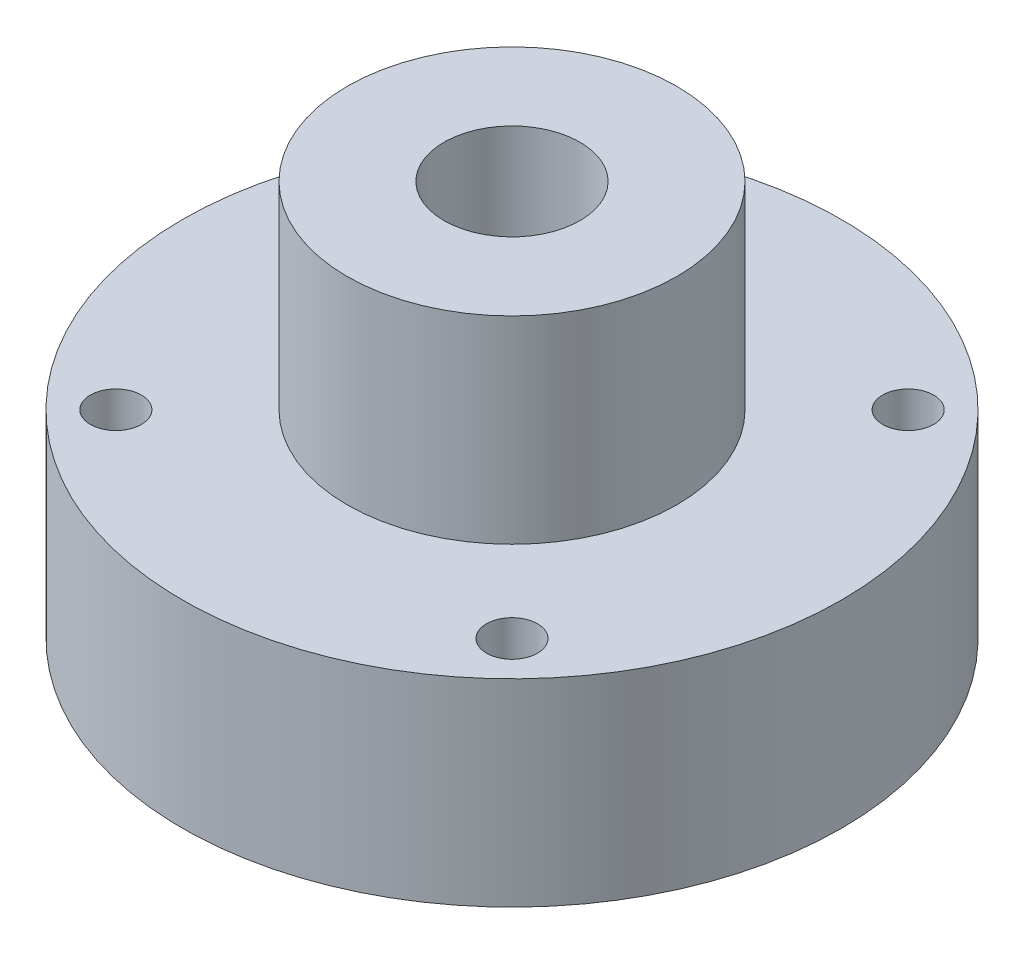
SolidWorks part; units mm, degrees
material "6061-T6 (SS)"
ref_plane "Front Plane" through (0, 0, 0) normal (0, 0, 1) x (1, 0, 0)
ref_plane "Top Plane" through (0, 0, 0) normal (0, 1, 0) x (1, 0, 0)
ref_plane "Right Plane" through (0, 0, 0) normal (1, 0, 0) x (0, 0, -1)
sketch "Sketch1" plane through (0, 0, 0) normal (0, 0, 1) x (1, 0, 0)
  line L0 (0, 0) -> (0, -5.2937) construction
  line L6 (-12.7, -19.05) -> (-12.7, -38.1)
  line L9 (-31.75, 0) -> (-31.75, -38.1)
  line L12 (-12.7, -19.05) -> (-3.175, -19.05)
  line L15 (-19.0373, -38.1) -> (-12.7, -38.1)
  line L17 (-31.75, -38.1) -> (-23.8125, -38.1)
  line L18 (-23.8125, -38.1) -> (-23.8125, -34.9631)
  line L19 (-23.8125, -34.9631) -> (-19.0373, -34.9631)
  line L20 (-19.0373, -34.9631) -> (-19.0373, -38.1)
  line L24 (-12.7, -38.1) -> (-3.175, -19.05)
  line L25 (-31.75, 0) -> (-3.175, 0)
  line L26 (-3.175, 0) -> (-3.175, -19.05)
  line L27 (-31.75, -19.05) -> (-15.875, -19.05)
  line L28 (-15.875, -19.05) -> (-15.875, 0)
  spline S0 degree 3 poles (6.8653, -14.0383) (6.7746, -14.0297) (6.669, -14.0211) (6.2404, -13.9904) (5.8365, -13.9684) (4.8724, -13.9243) (4.3124, -13.9022) (3.084, -13.8581) (2.4159, -13.8361) (1.0289, -13.792) (0.3103, -13.77) (-1.1159, -13.7259) (-1.8233, -13.7038) (-3.1659, -13.6597) (-3.8009, -13.6377) (-4.9442, -13.5936) (-5.4523, -13.5715) (-6.2976, -13.5274) (-6.6348, -13.5054) (-7.1093, -13.4613) (-7.3837, -13.4172) (-7.2343, -13.3731) (-6.8792, -13.329) (-6.5989, -13.3069) (-5.8566, -13.2628) (-5.3947, -13.2408) (-4.3289, -13.1967) (-3.7251, -13.1746) (-2.4274, -13.1305) (-1.7337, -13.1085) (-0.3158, -13.0644) (0.4082, -13.0423) (1.8242, -12.9983) (2.5161, -12.9762) (3.8083, -12.9321) (4.4084, -12.9101) (5.4653, -12.866) (5.922, -12.8439) (6.6525, -12.7998) (6.9263, -12.7778) (7.2673, -12.7337) (7.4017, -12.6896) (7.1111, -12.6455) (6.6204, -12.6014) (6.275, -12.5793) (5.4137, -12.5352) (4.8979, -12.5132) (3.74, -12.4691) (3.0981, -12.447) (1.7433, -12.4029) (1.0305, -12.3809) (-0.4048, -12.3368) (-1.1271, -12.3147) (-2.5192, -12.2706) (-3.1888, -12.2486) (-4.4177, -12.2045) (-4.9769, -12.1825) (-5.9368, -12.1384) (-6.3373, -12.1163) (-6.9452, -12.0722) (-7.1525, -12.0502) (-7.3559, -12.0061) (-7.352, -11.984) (-7.1332, -11.9399) (-6.9183, -11.9179) (-6.2959, -11.8738) (-5.8884, -11.8517) (-4.9158, -11.8076) (-4.3507, -11.7856) (-3.1114, -11.7415) (-2.4374, -11.7194) (-1.0381, -11.6753) (-0.313, -11.6533) (1.1259, -11.6092) (1.8395, -11.5871) (3.194, -11.543) (3.8347, -11.521) (4.9881, -11.4769) (5.5007, -11.4548) (6.3536, -11.4108) (6.6938, -11.3887) (7.1724, -11.3446) (7.4493, -11.3005) (7.2985, -11.2564) (6.9403, -11.2123) (6.6574, -11.1903) (5.9085, -11.1462) (5.4425, -11.1241) (4.3673, -11.08) (3.7581, -11.058) (2.4489, -11.0139) (1.749, -10.9918) (0.3186, -10.9477) (-0.4118, -10.9257) (-1.8404, -10.8816) (-2.5384, -10.8595) (-3.842, -10.8154) (-4.4475, -10.7934) (-5.5138, -10.7493) (-5.9745, -10.7272) (-6.7114, -10.6831) (-6.9876, -10.6611) (-7.3316, -10.617) (-7.4672, -10.5729) (-7.174, -10.5288) (-6.679, -10.4847) (-6.3305, -10.4627) (-5.4616, -10.4186) (-4.9412, -10.3965) (-3.7731, -10.3524) (-3.1255, -10.3304) (-1.7587, -10.2863) (-1.0396, -10.2642) (0.4084, -10.2201) (1.1371, -10.1981) (2.5414, -10.154) (3.217, -10.1319) (4.4567, -10.0878) (5.0209, -10.0658) (5.9892, -10.0217) (6.3932, -9.9996) (7.0065, -9.9555) (7.2156, -9.9335) (7.4209, -9.8894) (7.4169, -9.8673) (7.1962, -9.8233) (6.9794, -9.8012) (6.3515, -9.7571) (5.9404, -9.7351) (4.9591, -9.691) (4.3891, -9.6689) (3.1389, -9.6248) (2.4589, -9.6028) (1.0472, -9.5587) (0.3158, -9.5366) (-1.1358, -9.4925) (-1.8557, -9.4705) (-3.2221, -9.4264) (-3.8685, -9.4043) (-5.0321, -9.3602) (-5.5491, -9.3382) (-6.4095, -9.2941) (-6.7527, -9.272) (-7.2356, -9.2279) (-7.5148, -9.1838) (-7.3627, -9.1397) (-7.0013, -9.0956) (-6.716, -9.0736) (-5.9605, -9.0295) (-5.4904, -9.0075) (-4.4056, -8.9634) (-3.7911, -8.9413) (-2.4704, -8.8972) (-1.7644, -8.8752) (-0.3214, -8.8311) (0.4154, -8.809) (1.8566, -8.7649) (2.5607, -8.7429) (3.8757, -8.6988) (4.4865, -8.6767) (5.5622, -8.6326) (6.0269, -8.6106) (6.7704, -8.5665) (7.049, -8.5444) (7.396, -8.5003) (7.5327, -8.4562) (7.237, -8.4121) (6.7375, -8.368) (6.386, -8.346) (5.5095, -8.3019) (4.9846, -8.2798) (3.8062, -8.2358) (3.1529, -8.2137) (1.7741, -8.1696) (1.0487, -8.1476) (-0.412, -8.1035) (-1.147, -8.0814) (-2.5637, -8.0373) (-3.2451, -8.0153) (-4.4958, -7.9712) (-5.0648, -7.9491) (-6.0416, -7.905) (-6.4492, -7.883) (-7.0678, -7.8389) (-7.2788, -7.8168) (-7.4858, -7.7727) (-7.4818, -7.7507) (-7.2591, -7.7066) (-7.0404, -7.6845) (-6.407, -7.6404) (-5.9923, -7.6184) (-5.0025, -7.5743) (-4.4275, -7.5522) (-3.1663, -7.5081) (-2.4803, -7.4861) (-1.0564, -7.442) (-0.3185, -7.42) (1.1457, -7.3759) (1.8719, -7.3538) (3.2503, -7.3097) (3.9023, -7.2877) (5.076, -7.2436) (5.5976, -7.2215) (6.4655, -7.1774) (6.8116, -7.1554) (7.2987, -7.1113) (7.5804, -7.0672) (7.4269, -7.0231) (7.0624, -6.979) (6.7746, -6.9569) (6.0125, -6.9128) (5.5382, -6.8908) (4.444, -6.8467) (3.8242, -6.8246) (2.492, -6.7805) (1.7798, -6.7585) (0.3242, -6.7144) (-0.4191, -6.6923) (-1.8727, -6.6483) (-2.583, -6.6262) (-3.9095, -6.5821) (-4.5256, -6.5601) (-5.6106, -6.516) (-6.0794, -6.4939) (-6.8293, -6.4498) (-7.1103, -6.4278) (-7.4603, -6.3837) (-7.5982, -6.3396) (-7.2999, -6.2955) (-6.7961, -6.2514) (-6.4416, -6.2293) (-5.5574, -6.1852) (-5.0279, -6.1632) (-3.8393, -6.1191) (-3.1803, -6.097) (-1.7895, -6.0529) (-1.0578, -6.0309) (0.4155, -5.9868) (1.157, -5.9647) (2.586, -5.9206) (3.2733, -5.8986) (4.5348, -5.8545) (5.1088, -5.8325) (6.094, -5.7884) (6.5052, -5.7663) (7.1291, -5.7222) (7.3419, -5.7002) (7.5507, -5.6561) (7.5467, -5.634) (7.322, -5.5899) (7.1015, -5.5679) (6.4625, -5.5238) (6.0443, -5.5017) (5.0458, -5.4576) (4.4658, -5.4356) (3.1937, -5.3915) (2.5018, -5.3694) (1.0655, -5.3253) (0.3213, -5.3033) (-1.1556, -5.2592) (-1.8881, -5.2371) (-3.2784, -5.193) (-3.936, -5.171) (-5.1199, -5.1269) (-5.646, -5.1048) (-6.5214, -5.0608) (-6.8705, -5.0387) (-7.3618, -4.9946) (-7.6459, -4.9505) (-7.4912, -4.9064) (-7.1234, -4.8623) (-6.8331, -4.8403) (-6.0644, -4.7962) (-5.5861, -4.7741) (-4.4824, -4.73) (-3.8572, -4.708) (-2.5135, -4.6639) (-1.7951, -4.6418) (-0.327, -4.5977) (0.4227, -4.5757) (1.8889, -4.5316) (2.6053, -4.5095) (3.9432, -4.4654) (4.5646, -4.4434) (5.659, -4.3993) (6.1318, -4.3772) (6.8882, -4.3331) (7.1716, -4.3111) (7.5246, -4.267) (7.6637, -4.2229) (7.3628, -4.1788) (6.8547, -4.1347) (6.4971, -4.1127) (5.6053, -4.0686) (5.0712, -4.0465) (3.8723, -4.0024) (3.2077, -3.9804) (1.8049, -3.9363) (1.0669, -3.9142) (-0.4191, -3.8701) (-1.167, -3.8481) (-2.6082, -3.804) (-3.3015, -3.7819) (-4.5226, -3.7396) (-5.0592, -3.7193) (-5.5281, -3.6991) knots 0.041447 0.041447 0.041447 0.041447 0.042969 0.042969 0.046875 0.046875 0.050781 0.050781 0.054688 0.054688 0.058594 0.058594 0.0625 0.0625 0.066406 0.066406 0.070312 0.070312 0.074219 0.074219 0.078125 0.082031 0.082031 0.085938 0.085938 0.089844 0.089844 0.09375 0.09375 0.097656 0.097656 0.101562 0.101562 0.105469 0.105469 0.109375 0.109375 0.113281 0.113281 0.117188 0.117188 0.121094 0.125 0.125 0.128906 0.128906 0.132812 0.132812 0.136719 0.136719 0.140625 0.140625 0.144531 0.144531 0.148438 0.148438 0.152344 0.152344 0.15625 0.15625 0.160156 0.160156 0.164062 0.164062 0.167969 0.167969 0.171875 0.171875 0.175781 0.175781 0.179688 0.179688 0.183594 0.183594 0.1875 0.1875 0.191406 0.191406 0.195312 0.195312 0.199219 0.199219 0.203125 0.207031 0.207031 0.210938 0.210938 0.214844 0.214844 0.21875 0.21875 0.222656 0.222656 0.226562 0.226562 0.230469 0.230469 0.234375 0.234375 0.238281 0.238281 0.242188 0.242188 0.246094 0.25 0.25 0.253906 0.253906 0.257812 0.257812 0.261719 0.261719 0.265625 0.265625 0.269531 0.269531 0.273438 0.273438 0.277344 0.277344 0.28125 0.28125 0.285156 0.285156 0.289062 0.289062 0.292969 0.292969 0.296875 0.296875 0.300781 0.300781 0.304688 0.304688 0.308594 0.308594 0.3125 0.3125 0.316406 0.316406 0.320312 0.320312 0.324219 0.324219 0.328125 0.332031 0.332031 0.335938 0.335938 0.339844 0.339844 0.34375 0.34375 0.347656 0.347656 0.351562 0.351562 0.355469 0.355469 0.359375 0.359375 0.363281 0.363281 0.367188 0.367188 0.371094 0.375 0.375 0.378906 0.378906 0.382812 0.382812 0.386719 0.386719 0.390625 0.390625 0.394531 0.394531 0.398438 0.398438 0.402344 0.402344 0.40625 0.40625 0.410156 0.410156 0.414062 0.414062 0.417969 0.417969 0.421875 0.421875 0.425781 0.425781 0.429688 0.429688 0.433594 0.433594 0.4375 0.4375 0.441406 0.441406 0.445312 0.445312 0.449219 0.449219 0.453125 0.457031 0.457031 0.460938 0.460938 0.464844 0.464844 0.46875 0.46875 0.472656 0.472656 0.476562 0.476562 0.480469 0.480469 0.484375 0.484375 0.488281 0.488281 0.492188 0.492188 0.496094 0.5 0.5 0.503906 0.503906 0.507812 0.507812 0.511719 0.511719 0.515625 0.515625 0.519531 0.519531 0.523438 0.523438 0.527344 0.527344 0.53125 0.53125 0.535156 0.535156 0.539062 0.539062 0.542969 0.542969 0.546875 0.546875 0.550781 0.550781 0.554688 0.554688 0.558594 0.558594 0.5625 0.5625 0.566406 0.566406 0.570312 0.570312 0.574219 0.574219 0.578125 0.582031 0.582031 0.585938 0.585938 0.589844 0.589844 0.59375 0.59375 0.597656 0.597656 0.601562 0.601562 0.605469 0.605469 0.609375 0.609375 0.613281 0.613281 0.617188 0.617188 0.621094 0.625 0.625 0.628906 0.628906 0.632812 0.632812 0.636719 0.636719 0.640625 0.640625 0.644531 0.644531 0.648438 0.648438 0.652029 0.652029 0.652029 0.652029 construction
  dimension "D2" = 25.4
  dimension "D3" = 19.05
  dimension "D4" = 6.35
  dimension "D5" = 38.1
  dimension "D6" = 26.565
  dimension "D7" = 63.5
  dimension "D8" = 31.75
  dimension "D9" = 4.7752
  dimension "D10" = 19.05
  dimension "D12" = 47.625
  dimension "D13" = 3.1369
revolve "Revolve1" add sketch "Sketch1" angle 360 about L0 region at (-9.525, -25.4, 0) region at (-17.0363, -20.5594, 0)
hole_wizard "#10 (0.1935) Diameter Hole1" positions "Sketch2" profile "Sketch3" hole size "#10" standard "ANSI Inch" end condition through all
sketch "Sketch2" plane through (0, 0, 0) normal (0, 1, 0) x (1, 0, 0)
  line L0 (-19.083, 19.083) -> (19.083, -19.083) construction
  line L2 (19.083, 19.083) -> (-19.083, -19.083) construction
  line L3 (0, 0) -> (-24.6236, 0) construction
  point P0 (19.083, 19.083)
  point P2 (-19.083, 19.083)
  point P4 (-19.083, -19.083)
  point P6 (19.083, -19.083)
  dimension "D1" = 53.975
  dimension "D2" = 45
sketch "Sketch3" plane through (19.083, 0, -19.083) normal (1, 0, 0) x (0, 0, 1)
  line L0 (0, 0) -> (0, 38.1)
  line L1 (0, 38.1) -> (2.4574, 38.1)
  line L2 (2.4574, 38.1) -> (2.4574, 0)
  line L5 (2.4574, 0) -> (0, 0)
  line L11 (0, -6.35) -> (0, 107.95) construction
  dimension "Thru Hole Dia." = 4.9149
  dimension "Thru Hole Depth" = 38.1
hole_wizard "33/64 (0.51563) Diameter Hole1" positions "3DSketch1" profile "Sketch4" hole size "33/64" standard "ANSI Inch" end condition through all
sketch3d "3DSketch1"
  circle A3 centre (0, 0, 0) radius 3.175 construction
  point P0 (0, 0, 0)
  point P21 (0, 3.175, 0)
  point P24 (0, 0, 0)
sketch "Sketch4" plane through (0, 0, 0) normal (1, 0, 0) x (0, 0, 1)
  line L0 (0, 0) -> (0, 38.1)
  line L1 (0, 38.1) -> (6.5485, 38.1)
  line L2 (6.5485, 38.1) -> (6.5485, 0)
  line L5 (6.5485, 0) -> (0, 0)
  line L11 (0, -6.35) -> (0, 107.95) construction
  dimension "Thru Hole Dia." = 13.097
  dimension "Thru Hole Depth" = 38.1
sketch "Sketch5" plane through (0, -38.1, 0) normal (0, 1, 0) x (1, 0, 0)
  circle A0 centre (0, 0) radius 38.1
  dimension "D1" = 76.2
ref_plane "Plane1" through (0, 0, 0) normal (0, -1, 0) x (-1, 0, 0)
